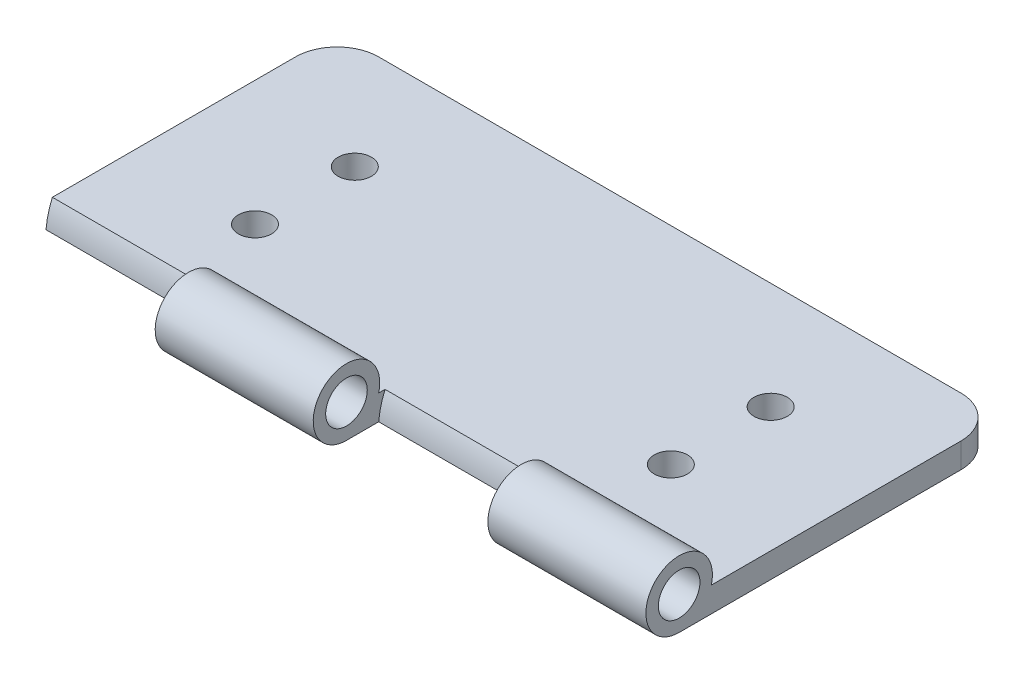
SolidWorks part; units mm, degrees
ref_plane "Front Plane" through (0, 0, 0) normal (0, 0, 1) x (1, 0, 0)
ref_plane "Top Plane" through (0, 0, 0) normal (0, 1, 0) x (1, 0, 0)
ref_plane "Right Plane" through (0, 0, 0) normal (1, 0, 0) x (0, 0, -1)
sketch "Sketch1" plane through (0, 0, 0) normal (0, 1, 0) x (1, 0, 0)
  line L1 (-35, 17.5) -> (35, 17.5)
  line L2 (-40, 12.5) -> (-40, -17.5)
  line L3 (-40, -17.5) -> (40, -17.5)
  line L4 (40, 12.5) -> (40, -17.5)
  line L5 (-40, 17.5) -> (40, -17.5) construction
  line L6 (-40, -17.5) -> (40, 17.5) construction
  arc A0 (-40, 12.5) -> (-35, 17.5) centre (-35, 12.5) cw
  arc A1 (40, 12.5) -> (35, 17.5) centre (35, 12.5) ccw
  point P0 (0, 0)
  dimension "D3" = 5
  dimension "D1" = 80
  dimension "D2" = 35
extrude "Boss-Extrude1" add sketch "Sketch1" along normal blind 3
sketch "Sketch2" plane through (40, 0, 0) normal (1, 0, 0) x (0, 0, -1)
  line L1 (-17.4974, 0) -> (-21.373, 0)
  line L2 (-17.5, 0) -> (12.5, 0) construction
  arc A0 (-17.5, 3) -> (-21.373, 0) centre (-21.373, 4) ccw
  circle A1 centre (-21.373, 4) radius 2.5
  line M4 (-17.5, 3) -> (-17.5, 0)
  dimension "D1" = 8
  dimension "D2" = 5
extrude "Boss-Extrude2" add sketch "Sketch2" against normal blind 19 contours A0 L1 A1 M4 region at (40, 0.1131, 19.4365)
pattern_linear "LPattern1" count 2 spacing 40 along (-1, 0, 0) of "Boss-Extrude2"
chamfer "Chamfer3" distance 1 angle 32 2 edges at (10.5, 3, 17.5) (-29.5, 3, 17.5) first distance on face at (10.5, 1.5, 17.5) first distance on face at (-29.5, 1.5, 17.5)
fillet "Fillet1" radius 10 2 edges at (10.5, 2, 17.5) (-29.5, 2, 17.5)
sketch "스케치1" plane through (0, 0, 0) normal (0, -1, 0) x (1, 0, 0)
  line L0 (-40, -12.5) -> (-40, 17.5) construction
  line L1 (-19, 21.373) -> (0, 21.373) construction
  line L2 (21, 21.373) -> (40, 21.373) construction
  line L3 (40, 21.373) -> (40, -12.5) construction
  line L4 (-40, 17.5) -> (-19, 17.5) construction
  line L5 (-19, 17.5) -> (-19, 21.373) construction
  line L6 (0, 17.5) -> (21, 17.5) construction
  circle A0 centre (-25, 7.373) radius 2
  circle A1 centre (-25, -4.627) radius 2
  circle A2 centre (25, 7.373) radius 2
  circle A3 centre (25, -4.627) radius 2
  dimension "D1" = 15
  dimension "D2" = 15
  dimension "D3" = 14
  dimension "D4" = 12
  dimension "D5" = 14
  dimension "D6" = 12
  dimension "D7" = 15
extrude "컷-돌출1" cut sketch "스케치1" against normal through all
